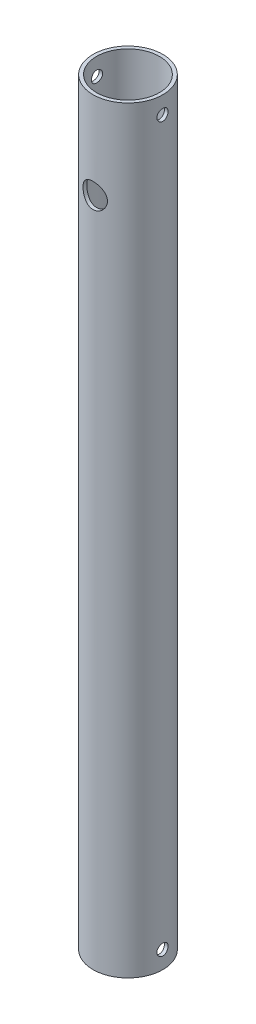
SolidWorks part; units mm, degrees
material "Toray T700"
ref_plane "Front" through (0, 0, 0) normal (0, 0, 1) x (1, 0, 0)
ref_plane "Top" through (0, 0, 0) normal (0, 1, 0) x (1, 0, 0)
ref_plane "Right" through (0, 0, 0) normal (1, 0, 0) x (0, 0, -1)
sketch "Sketch1" plane through (0, 0, 0) normal (0, 1, 0) x (1, 0, 0)
  line L5 (4.7969, 0) -> (-5.97, 0) construction
  circle A0 centre (0, 0) radius 10
  circle A1 centre (0, 0) radius 9
  dimension "D1" = 20
  dimension "D2" = 18
extrude "Boss-Extrude1" add sketch "Sketch1" along normal blind 217
ref_axis "Axis1" through (0, 217, 0) along (0, -1, 0)
ref_plane "Plane1" through (-10, 0, 0) normal (-1, 0, 0) x (0, 0, 1)
hole_wizard "M3 Clearance Hole1" positions "Sketch3" profile "Sketch2" hole size "M3" standard "DIN" end condition through all
sketch "Sketch3" plane through (-10, 0, 0) normal (-1, 0, 0) x (0, 0, 1)
  line L0 (-9, 0) -> (9, 0) construction
  line L1 (0, -50) -> (0, 50) construction
  point P0 (0, 5)
  dimension "D1" = 5
sketch "Sketch2" plane through (-10, 5, 0) normal (0, 1, 0) x (0, 0, 1)
  line L0 (0, 0) -> (0, 20)
  line L1 (0, 20) -> (1.6, 20)
  line L2 (1.6, 20) -> (1.6, 0)
  line L5 (1.6, 0) -> (0, 0)
  line L11 (0, -6.35) -> (0, 107.95) construction
  dimension "Thru Hole Dia." = 3.2
  dimension "Thru Hole Depth" = 20
ref_plane "Plane2" through (0, 108.5, 0) normal (0, 1, 0) x (1, 0, 0)
mirror "Mirror1" about plane through (0, 108.5, 0) normal (0, 1, 0) of "M3 Clearance Hole1"
ref_plane "Plane3" through (0, 0, -10) normal (0, 0, -1) x (-1, 0, 0)
sketch "Sketch4" plane through (0, 0, -10) normal (0, 0, -1) x (-1, 0, 0)
  line L0 (-10, 0) -> (10, 0) construction
  circle A0 centre (0, 25) radius 3.5
  dimension "D1" = 7
  dimension "D2" = 25
extrude "Cut-Extrude1" cut sketch "Sketch4" against normal up to next
ref_plane "Plane4" through (0, 0, 10) normal (0, 0, 1) x (1, 0, 0)
sketch "Sketch5" plane through (0, 0, 10) normal (0, 0, 1) x (1, 0, 0)
  line L0 (10, 217) -> (-10, 217) construction
  line L2 (9, 217) -> (-9, 217) construction
  line L3 (0, 192) -> (0, 217) construction
  circle A0 centre (0, 192) radius 3.5
  dimension "D2" = 7
  dimension "D1" = 25
extrude "Cut-Extrude2" cut sketch "Sketch5" against normal up to next
